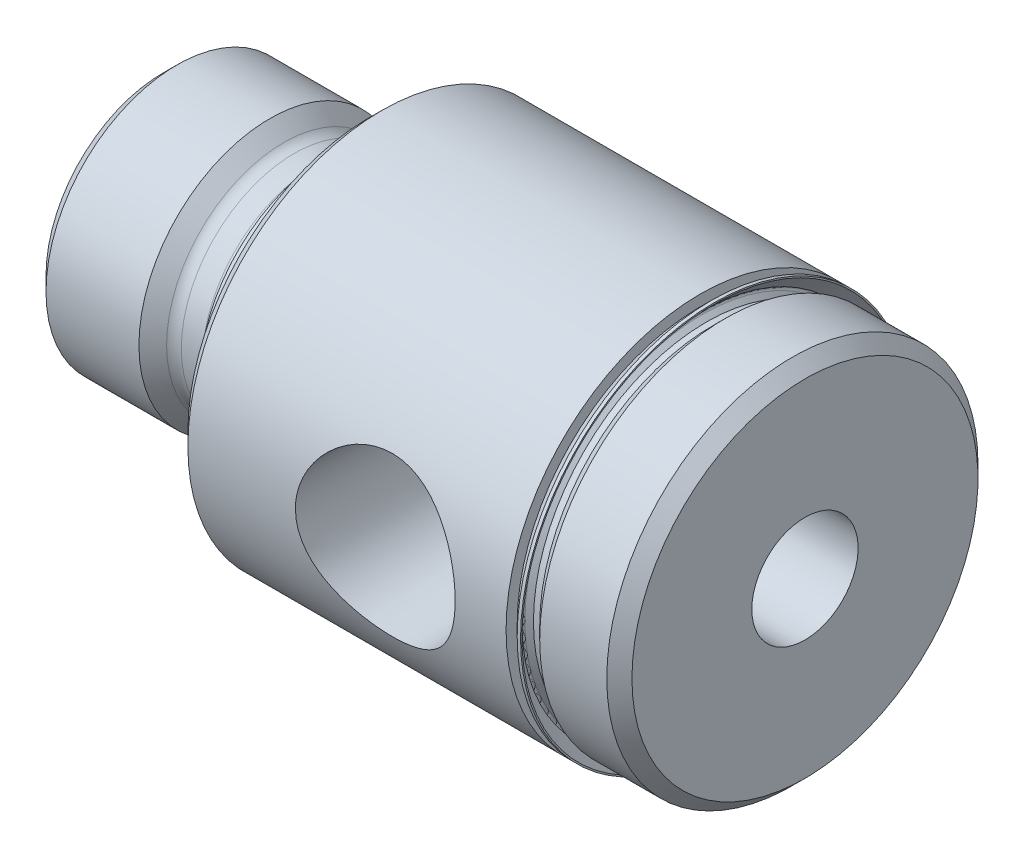
SolidWorks part; units mm, degrees
material "Cast Alloy Steel"
ref_plane "Front Plane" through (0, 0, 0) normal (0, 0, 1) x (1, 0, 0)
ref_plane "Top Plane" through (0, 0, 0) normal (0, 1, 0) x (1, 0, 0)
ref_plane "Right Plane" through (0, 0, 0) normal (1, 0, 0) x (0, 0, -1)
sketch "Sketch1" plane through (0, 0, 0) normal (0, 0, 1) x (1, 0, 0)
  line L0 (0, 0) -> (0, 7.098)
  line L1 (0, 7.098) -> (0.8395, 7.9375)
  line L2 (0.8395, 7.9375) -> (6.4694, 7.9375)
  line L3 (6.4694, 7.9375) -> (7.3094, 7.0988)
  line L4 (7.9375, 6.8389) -> (9.2202, 6.8389)
  line L5 (10.1092, 7.728) -> (10.1092, 7.9057)
  line L6 (10.1092, 7.9057) -> (12.4968, 7.9057)
  line L7 (12.4968, 7.9057) -> (12.4968, 0)
  line L8 (12.4968, 0) -> (0, 0)
  line L9 (12.4968, 0) -> (0, 0) construction
  arc A0 (7.3094, 7.0988) -> (7.9375, 6.8389) centre (7.9375, 7.728) ccw
  arc A1 (9.2202, 6.8389) -> (10.1092, 7.728) centre (9.2202, 7.728) ccw
revolve "Revolve1" add sketch "Sketch1" angle 360 about L9 reverse direction yes
cosmetic thread "Cosmetic Thread1" parameters "D1"=7.3089, "D2"=14.1961
sketch "Sketch2" plane through (0, 0, 0) normal (0, 0, 1) x (1, 0, 0)
  line L0 (12.4968, 0) -> (12.4968, 10.9982)
  line L1 (12.4968, 10.9982) -> (13.2588, 11.7602)
  line L2 (13.2588, 11.7602) -> (32.5374, 11.7602)
  line L3 (32.5374, 11.7602) -> (32.5374, 10.4839)
  line L4 (32.5374, 10.4839) -> (33.2994, 10.4839)
  line L5 (33.2994, 10.4839) -> (34.0614, 11.2459)
  line L6 (34.0614, 11.2459) -> (38.1254, 11.2459)
  line L7 (38.1254, 11.2459) -> (38.8874, 10.4839)
  line L8 (38.8874, 10.4839) -> (38.8874, 0)
  line L9 (38.8874, 0) -> (12.4968, 0)
  line L10 (38.8874, 0) -> (12.4968, 0) construction
revolve "Revolve2" add sketch "Sketch2" angle 360 about L10 reverse direction yes
hole_wizard "Hole1" positions "Sketch4" profile "Sketch3" legacy
sketch "Sketch4" plane through (0, 0, 0) normal (-1, 0, 0) x (0, 0, 1)
  point P0 (0, 0)
sketch "Sketch3" plane through (0, 0, 0) normal (0, 1, 0) x (0, 0, 1)
  line L0 (0, 0) -> (0, 38.8874)
  line L1 (0, 38.8874) -> (3.2195, 38.8874)
  line L2 (3.2195, 38.8874) -> (3.2195, 0.762)
  line L3 (3.2195, 0.762) -> (3.9815, 0)
  line L4 (3.9815, 0) -> (0, 0)
  line L5 (0, -6.4453) -> (0, 115.525) construction
  line L6 (-3.2195, 0.762) -> (-3.9815, 0) construction
  dimension "Diameter" = 6.4389
  dimension "Depth" = 38.8874
  dimension "C-Sink Angle" = 90
  dimension "C-Sink Diameter" = 7.9629
ref_plane "Plane1" through (0, 0, 0) normal (1, 0, 0) x (0, 0, -1)
ref_plane "Plane2" through (0, 0, 0) normal (1, 0, 0) x (0, 0, -1)
ref_plane "Plane3" through (0, 0, 0) normal (0, -0.7071, 0.7071) x (1, 0, 0)
ref_plane "Plane4" through (0, 0, 0) normal (1, 0, 0) x (0, 0, -1)
ref_plane "Plane5" through (32.3342, 0, 0) normal (1, 0, 0) x (0, 0, -1)
ref_plane "Plane6" through (12.4968, 0, 0) normal (1, 0, 0) x (0, 0, -1)
ref_plane "Plane7" through (32.3342, 0, 0) normal (1, 0, 0) x (0, 0, -1)
sketch "Sketch5" plane through (0, 0, 0) normal (0, 1, 0) x (1, 0, 0)
  line L0 (24.6126, 0) -> (27.7876, 0)
  line L1 (27.7876, 0) -> (27.7876, -2.7136)
  line L2 (27.7876, -2.7136) -> (29.2142, -4.1402)
  line L3 (29.2142, -4.1402) -> (29.4521, -11.7602)
  line L4 (29.4521, -11.7602) -> (24.6126, -11.7602)
  line L5 (24.6126, -11.7602) -> (24.6126, 0)
  line L6 (24.6126, -11.7602) -> (24.6126, 0) construction
revolve "Cut-Revolve1" cut sketch "Sketch5" angle 360 about L6 reverse direction yes
cosmetic thread "Cosmetic Thread2" parameters "D1"=4.572, "D2"=10.287
sketch "Sketch6" plane through (0, 0, 0) normal (0, 0, 1) x (1, 0, 0)
  line L0 (32.5374, 10.2299) -> (33.2994, 10.2299)
  line L1 (33.2994, 10.2299) -> (33.2994, 10.4839)
  line L2 (33.2994, 10.4839) -> (32.9184, 10.4839)
  line L3 (32.9184, 10.4839) -> (32.6599, 10.7424)
  line L4 (32.6599, 10.922) -> (33.414, 11.676)
  line L5 (33.414, 11.676) -> (33.414, 11.7602)
  line L6 (33.414, 11.7602) -> (33.2108, 11.7602)
  line L7 (33.2108, 11.7602) -> (32.5374, 11.0868)
  line L8 (32.5374, 11.0868) -> (32.5374, 10.2299)
  line L9 (33.2994, 0) -> (32.5374, 0) construction
  arc A0 (32.6599, 10.7424) -> (32.6599, 10.922) centre (32.7497, 10.8322) cw
revolve "Revolve3" add sketch "Sketch6" angle 360 about L9 reverse direction yes
ref_plane "Plane8" through (33.2994, 0, 0) normal (1, 0, 0) x (0, 0, -1)
ref_plane "Plane9" through (12.4968, 0, 0) normal (1, 0, 0) x (0, 0, -1)
ref_plane "Plane10" through (10.1092, 0, 0) normal (1, 0, 0) x (0, 0, -1)
ref_plane "Plane11" through (0, 0, 0) normal (0, 1, 0) x (1, 0, 0)
ref_plane "Plane12" through (0, 0, 0) normal (0, 1, 0) x (1, 0, 0)
ref_plane "Plane13" through (12.4968, 0, 0) normal (1, 0, 0) x (0, 0, -1)
ref_plane "Plane14" through (0, 0, 0) normal (0, 0, 1) x (1, 0, 0)
ref_plane "Plane15" through (0, 0, 0) normal (0, 1, 0) x (1, 0, 0)
ref_plane "Plane16" through (0, 0, 0) normal (0, 1, 0) x (1, 0, 0)
ref_plane "Plane17" through (0, 0, 0) normal (0, 1, 0) x (1, 0, 0)
ref_plane "Plane18" through (0, 0, 0) normal (1, 0, 0) x (0, 0, -1)
ref_plane "dp1 XY" through (0, 0, 0) normal (0, 0, 1) x (1, 0, 0)
ref_plane "dp1 XZ" through (0, 7.9057, 0) normal (0, -1, 0) x (-1, 0, 0)
ref_plane "dp1 YZ" through (12.4968, 0, 0) normal (1, 0, 0) x (0, 0, -1)
ref_axis "dp1 X" through (-80.9, 7.9057, 0) along (1, 0, 0)
ref_axis "dp1 Y" through (12.4968, -50, 0) along (0, 1, 0)
ref_axis "dp1 Z" through (12.4968, 7.9057, 80.9) along (0, 0, -1)
sketch3d "dp1"
  point P0 (12.4968, 7.9057, 0)
ref_plane "dp2 XY" through (0, 0, 0) normal (0, 0, 1) x (1, 0, 0)
ref_plane "dp2 XZ" through (0, -7.9057, 0) normal (0, -1, 0) x (-1, 0, 0)
ref_plane "dp2 YZ" through (12.4968, 0, 0) normal (1, 0, 0) x (0, 0, -1)
ref_axis "dp2 X" through (-80.9, -7.9057, 0) along (1, 0, 0)
ref_axis "dp2 Y" through (12.4968, -50, 0) along (0, 1, 0)
ref_axis "dp2 Z" through (12.4968, -7.9057, 80.9) along (0, 0, -1)
sketch3d "dp2"
  point P0 (12.4968, -7.9057, 0)
ref_plane "port XY" through (0, 0, 0) normal (0, 0, 1) x (1, 0, 0)
ref_plane "port XZ" through (0, 0, 0) normal (0, -1, 0) x (-1, 0, 0)
ref_plane "port YZ" through (24.6126, 0, 0) normal (1, 0, 0) x (0, 0, -1)
ref_axis "port X" through (-80.9, 0, 0) along (1, 0, 0)
ref_axis "port Y" through (24.6126, -50, 0) along (0, 1, 0)
ref_axis "port Z" through (24.6126, 0, 80.9) along (0, 0, -1)
sketch3d "port"
  point P0 (24.6126, 0, 0)
ref_plane "rod_guide XY" through (0, 0, 0) normal (1, 0, 0) x (0, 0, -1)
ref_plane "rod_guide XZ" through (0, 0, 0) normal (0, -1, 0) x (-1, 0, 0)
ref_plane "rod_guide YZ" through (0, 0, 0) normal (0, 0, -1) x (-1, 0, 0)
ref_axis "rod_guide X" through (0, 0, 80.9) along (0, 0, -1)
ref_axis "rod_guide Y" through (0, -50, 0) along (0, 1, 0)
ref_axis "rod_guide Z" through (80.9, 0, 0) along (-1, 0, 0)
sketch3d "rod_guide"
  point P0 (0, 0, 0)
ref_plane "s1 XY" through (0, 0, 0) normal (0, 0, 1) x (1, 0, 0)
ref_plane "s1 XZ" through (0, 0, 0) normal (0, -1, 0) x (-1, 0, 0)
ref_plane "s1 YZ" through (10.1092, 0, 0) normal (1, 0, 0) x (0, 0, -1)
ref_axis "s1 X" through (-80.9, 0, 0) along (1, 0, 0)
ref_axis "s1 Y" through (10.1092, -50, 0) along (0, 1, 0)
ref_axis "s1 Z" through (10.1092, 0, 80.9) along (0, 0, -1)
sketch3d "s1"
  point P0 (10.1092, 0, 0)
ref_plane "s2 XY" through (0, 0, 0) normal (0, 0, 1) x (1, 0, 0)
ref_plane "s2 XZ" through (0, 0, 0) normal (0, -1, 0) x (-1, 0, 0)
ref_plane "s2 YZ" through (12.4968, 0, 0) normal (1, 0, 0) x (0, 0, -1)
ref_axis "s2 X" through (-80.9, 0, 0) along (1, 0, 0)
ref_axis "s2 Y" through (12.4968, -50, 0) along (0, 1, 0)
ref_axis "s2 Z" through (12.4968, 0, 80.9) along (0, 0, -1)
sketch3d "s2"
  point P0 (12.4968, 0, 0)
ref_plane "t1 XY" through (12.4968, 0, 0) normal (1, 0, 0) x (0, 0, -1)
ref_plane "t1 XZ" through (0, 0, 0) normal (0, -1, 0) x (-1, 0, 0)
ref_plane "t1 YZ" through (0, 0, 0) normal (0, 0, -1) x (-1, 0, 0)
ref_axis "t1 X" through (12.4968, 0, 80.9) along (0, 0, -1)
ref_axis "t1 Y" through (12.4968, -50, 0) along (0, 1, 0)
ref_axis "t1 Z" through (80.9, 0, 0) along (-1, 0, 0)
sketch3d "t1"
  point P0 (12.4968, 0, 0)
ref_plane "t111 XY" through (12.4968, 0, 0) normal (1, 0, 0) x (0, 0, -1)
ref_plane "t111 XZ" through (0, 0, 0) normal (0, -1, 0) x (-1, 0, 0)
ref_plane "t111 YZ" through (0, 0, 0) normal (0, 0, -1) x (-1, 0, 0)
ref_axis "t111 X" through (12.4968, 0, 80.9) along (0, 0, -1)
ref_axis "t111 Y" through (12.4968, -50, 0) along (0, 1, 0)
ref_axis "t111 Z" through (80.9, 0, 0) along (-1, 0, 0)
sketch3d "t111"
  point P0 (12.4968, 0, 0)
ref_plane "to_foot_bracket XY" through (12.4968, 0, 0) normal (1, 0, 0) x (0, 0, -1)
ref_plane "to_foot_bracket XZ" through (0, 0, 0) normal (0, -1, 0) x (-1, 0, 0)
ref_plane "to_foot_bracket YZ" through (0, 0, 0) normal (0, 0, -1) x (-1, 0, 0)
ref_axis "to_foot_bracket X" through (12.4968, 0, 80.9) along (0, 0, -1)
ref_axis "to_foot_bracket Y" through (12.4968, -50, 0) along (0, 1, 0)
ref_axis "to_foot_bracket Z" through (80.9, 0, 0) along (-1, 0, 0)
sketch3d "to_foot_bracket"
  point P0 (12.4968, 0, 0)
ref_plane "to_nut XY" through (10.1092, 0, 0) normal (1, 0, 0) x (0, 0, -1)
ref_plane "to_nut XZ" through (0, 0, 0) normal (0, -1, 0) x (-1, 0, 0)
ref_plane "to_nut YZ" through (0, 0, 0) normal (0, 0, -1) x (-1, 0, 0)
ref_axis "to_nut X" through (10.1092, 0, 80.9) along (0, 0, -1)
ref_axis "to_nut Y" through (10.1092, -50, 0) along (0, 1, 0)
ref_axis "to_nut Z" through (80.9, 0, 0) along (-1, 0, 0)
sketch3d "to_nut"
  point P0 (10.1092, 0, 0)
ref_plane "to_rod XY" through (0, 0, 0) normal (1, 0, 0) x (0, 0, -1)
ref_plane "to_rod XZ" through (0, 0, 0) normal (0, -1, 0) x (-1, 0, 0)
ref_plane "to_rod YZ" through (0, 0, 0) normal (0, 0, -1) x (-1, 0, 0)
ref_axis "to_rod X" through (0, 0, 80.9) along (0, 0, -1)
ref_axis "to_rod Y" through (0, -50, 0) along (0, 1, 0)
ref_axis "to_rod Z" through (80.9, 0, 0) along (-1, 0, 0)
sketch3d "to_rod"
  point P0 (0, 0, 0)
ref_plane "to_screw XY" through (0, 0, 0) normal (0, 1, 0) x (1, 0, 0)
ref_plane "to_screw XZ" through (0, 0, 0) normal (0, 0, 1) x (1, 0, 0)
ref_plane "to_screw YZ" through (24.6126, 0, 0) normal (1, 0, 0) x (0, 0, -1)
ref_axis "to_screw X" through (-80.9, 0, 0) along (1, 0, 0)
ref_axis "to_screw Y" through (24.6126, 0, 50) along (0, 0, -1)
ref_axis "to_screw Z" through (24.6126, 50, 0) along (0, -1, 0)
sketch3d "to_screw"
  point P0 (24.6126, 0, 0)
ref_plane "to_trunnion_brackets XY" through (0, 0, 0) normal (0, 1, 0) x (1, 0, 0)
ref_plane "to_trunnion_brackets XZ" through (0, 0, 0) normal (0, 0, 1) x (1, 0, 0)
ref_plane "to_trunnion_brackets YZ" through (0, 0, 0) normal (1, 0, 0) x (0, 0, -1)
ref_axis "to_trunnion_brackets X" through (-80.9, 0, 0) along (1, 0, 0)
ref_axis "to_trunnion_brackets Y" through (0, 0, 50) along (0, 0, -1)
ref_axis "to_trunnion_brackets Z" through (0, 50, 0) along (0, -1, 0)
sketch3d "to_trunnion_brackets"
  point P0 (0, 0, 0)
ref_plane "to_trunnion_brackets1 XY" through (0, 0, 0) normal (0, 1, 0) x (1, 0, 0)
ref_plane "to_trunnion_brackets1 XZ" through (0, 0, 0) normal (0, 0, 1) x (1, 0, 0)
ref_plane "to_trunnion_brackets1 YZ" through (0, 0, 0) normal (1, 0, 0) x (0, 0, -1)
ref_axis "to_trunnion_brackets1 X" through (-80.9, 0, 0) along (1, 0, 0)
ref_axis "to_trunnion_brackets1 Y" through (0, 0, 50) along (0, 0, -1)
ref_axis "to_trunnion_brackets1 Z" through (0, 50, 0) along (0, -1, 0)
sketch3d "to_trunnion_brackets1"
  point P0 (0, 0, 0)
ref_plane "to_trunnion_brackets2 XY" through (0, 0, 0) normal (0, 1, 0) x (1, 0, 0)
ref_plane "to_trunnion_brackets2 XZ" through (0, 0, 0) normal (0, 0, 1) x (1, 0, 0)
ref_plane "to_trunnion_brackets2 YZ" through (0, 0, 0) normal (1, 0, 0) x (0, 0, -1)
ref_axis "to_trunnion_brackets2 X" through (-80.9, 0, 0) along (1, 0, 0)
ref_axis "to_trunnion_brackets2 Y" through (0, 0, 50) along (0, 0, -1)
ref_axis "to_trunnion_brackets2 Z" through (0, 50, 0) along (0, -1, 0)
sketch3d "to_trunnion_brackets2"
  point P0 (0, 0, 0)
ref_plane "to_tube XY" through (33.2994, 0, 0) normal (1, 0, 0) x (0, 0, -1)
ref_plane "to_tube XZ" through (0, 0, 0) normal (0, -1, 0) x (-1, 0, 0)
ref_plane "to_tube YZ" through (0, 0, 0) normal (0, 0, -1) x (-1, 0, 0)
ref_axis "to_tube X" through (33.2994, 0, 80.9) along (0, 0, -1)
ref_axis "to_tube Y" through (33.2994, -50, 0) along (0, 1, 0)
ref_axis "to_tube Z" through (80.9, 0, 0) along (-1, 0, 0)
sketch3d "to_tube"
  point P0 (33.2994, 0, 0)
